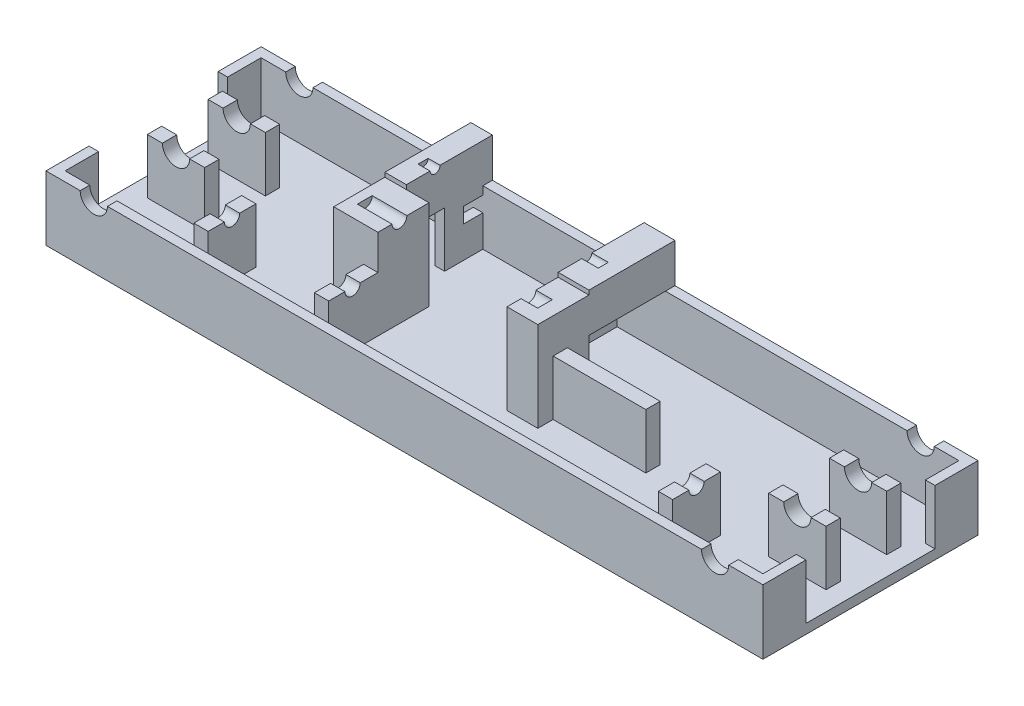
SolidWorks part; units mm, degrees
ref_plane "前视基准面" through (0, 0, 0) normal (0, 0, 1) x (1, 0, 0)
ref_plane "上视基准面" through (0, 0, 0) normal (0, 1, 0) x (1, 0, 0)
ref_plane "右视基准面" through (0, 0, 0) normal (1, 0, 0) x (0, 0, -1)
other "Configuration Table"
sketch "草图1" plane through (0, 0, 0) normal (0, 1, 0) x (1, 0, 0)
  line L1 (-75, -22.5) -> (75, -22.5)
  line L2 (-75, -22.5) -> (-75, 22.5)
  line L3 (-75, 22.5) -> (75, 22.5)
  line L4 (75, -22.5) -> (75, 22.5)
  line L5 (-75, -22.5) -> (75, 22.5) construction
  line L6 (-75, 22.5) -> (75, -22.5) construction
  point P0 (0, 0)
  dimension "D1" = 150
  dimension "D2" = 45
extrude "凸台-拉伸1" add sketch "草图1" along normal blind 2
sketch "草图2" plane through (0, 2, 0) normal (0, 1, 0) x (1, 0, 0)
  line L0 (-75, 22.5) -> (75, 22.5)
  line L1 (75, 22.5) -> (75, 13.5)
  line L2 (75, -22.5) -> (75, 22.5) construction
  line L3 (75, -22.5) -> (-75, -22.5)
  line L4 (-75, -22.5) -> (-75, -13.5)
  line L5 (-73, 20.5) -> (-28.6, 20.5)
  line L6 (73, 20.5) -> (73, 13.5)
  line L7 (73, -20.5) -> (-73, -20.5)
  line L8 (-73, -20.5) -> (-73, -13.5)
  line L9 (1.5, 20.5) -> (73, 20.5)
  line L23 (-1, 20.5) -> (-1, 12.5)
  line L24 (-73, 13.5) -> (-75, 13.5)
  line L25 (-75, -13.5) -> (-73, -13.5)
  line L26 (75, 13.5) -> (73, 13.5)
  line L27 (75, -13.5) -> (73, -13.5)
  line L28 (-75, 13.5) -> (-75, 22.5)
  line L29 (-73, 13.5) -> (-73, 20.5)
  line L30 (73, -13.5) -> (73, -20.5)
  line L31 (75, -13.5) -> (75, -22.5)
  line L32 (-1, 12.5) -> (1.5, 12.5)
  line L33 (-71, -2.3) -> (-59, -2.3)
  line L34 (-71, -2.3) -> (-71, -5.3)
  line L35 (-71, -5.3) -> (-59, -5.3)
  line L36 (-59, -2.3) -> (-59, -5.3)
  line L37 (-75, 22.5) -> (-75, -22.5) construction
  line L38 (59, -2.3) -> (71, -2.3)
  line L39 (59, -2.3) -> (59, -5.3)
  line L40 (59, -5.3) -> (71, -5.3)
  line L41 (71, -2.3) -> (71, -5.3)
  line L42 (75, -22.5) -> (75, 22.5) construction
  line L43 (-55, -5.4) -> (-75, -5.4) construction
  line L44 (75, -5.4) -> (55, -5.4) construction
  line L45 (66.4142, 10.5) -> (67.4958, 10.5) construction
  line L46 (-71, 10.4) -> (-59, 10.4)
  line L47 (-71, 10.4) -> (-71, 7.4)
  line L48 (-71, 7.4) -> (-59, 7.4)
  line L49 (-59, 10.4) -> (-59, 7.4)
  line L50 (59, 10.4) -> (71, 10.4)
  line L51 (59, 10.4) -> (59, 7.4)
  line L52 (59, 7.4) -> (71, 7.4)
  line L53 (71, 10.4) -> (71, 7.4)
  line L54 (-63.5858, 10.5) -> (-62.5042, 10.5) construction
  line L55 (1.5, 20.5) -> (1.5, 12.5)
  line L57 (-28.6, 20.5) -> (-28.6, 12.5)
  line L58 (-28.6, 12.5) -> (-26.6, 12.5)
  line L59 (-26.6, 20.5) -> (-26.6, 12.5)
  line L60 (-26.6, 20.5) -> (-1, 20.5)
  point P57 (-26.6, 16.5)
  dimension "D1" = 2
  dimension "D2" = 2
  dimension "D3" = 2
  dimension "D4" = 2
  dimension "D5" = 9
  dimension "D6" = 3
  dimension "D7" = 3
  dimension "D8" = 12
  dimension "D9" = 12
  dimension "D10" = 4
  dimension "D11" = 4
  dimension "D12" = 0.1
  dimension "D13" = 0.1
  dimension "D14" = 0.1
  dimension "D15" = 0.1
  dimension "D16" = 3
  dimension "D17" = 2.5
  dimension "D18" = 2
  dimension "D19" = 71.5
  dimension "D20" = 8
  dimension "D21" = 48.4
extrude "凸台-拉伸2" add sketch "草图2" along normal up to surface (11.5 mm away)
sketch "草图4" plane through (0, 2, 0) normal (0, 1, 0) x (1, 0, 0)
  line L1 (-50.0747, -6.5) -> (-47.0747, -6.5)
  line L2 (-50.0747, -6.5) -> (-50.0747, -16.5)
  line L3 (-50.0747, -16.5) -> (-47.0747, -16.5)
  line L4 (-47.0747, -6.5) -> (-47.0747, -16.5)
  line L5 (-31.1, 4.5) -> (-21.85, 4.5)
  line L6 (-31.1, 4.5) -> (-31.1, -6.2)
  line L7 (-24.85, -16.5) -> (-21.85, -16.5)
  line L8 (-21.85, 4.5) -> (-21.85, -16.5)
  line L9 (47.1147, -6.5) -> (50.1147, -6.5)
  line L10 (47.1147, -6.5) -> (47.1147, -16.5)
  line L11 (47.1147, -16.5) -> (50.1147, -16.5)
  line L12 (50.1147, -6.5) -> (50.1147, -16.5)
  line L13 (5.15, 4.5) -> (11.6, 4.5)
  line L14 (5.15, 4.5) -> (5.15, -6.2)
  line L15 (5.15, -6.2) -> (11.6, -6.2)
  line L16 (11.6, 4.5) -> (11.6, 0)
  line L26 (31, 0) -> (11.6, 0)
  line L28 (11.6, -3) -> (31, -3)
  line L31 (-50.2747, -15.25) -> (-50.2747, -7.75) construction
  line L32 (50.3147, -7.75) -> (50.3147, -15.25) construction
  line L33 (-29.7348, -10) -> (-29.7348, -13) construction
  line L34 (56.24, -10) -> (-56.2, -10) construction
  line L35 (-56.2, -13) -> (56.24, -13) construction
  line L36 (-29.7348, -11.5) -> (-37.5732, -11.5) construction
  line L37 (-21.55, -10.8234) -> (-21.55, -11.245) construction
  line L38 (31, 0) -> (31, -3)
  line L40 (11.6, -3) -> (11.6, -6.2)
  line L41 (75, -13.5) -> (75, 13.5) construction
  line L42 (-26.35, -3.2) -> (7.05, -3.2) construction
  line L43 (-31.1, -6.2) -> (-24.85, -6.2)
  line L44 (-24.85, -6.2) -> (-24.85, -16.5)
  line L45 (11.7, 3.8856) -> (11.7, 17.1144) construction
  line L46 (5.05, 2.196) -> (5.05, 3.4405) construction
  line L47 (-75, 13.5) -> (-75, -13.5) construction
  line L48 (-73, 20.5) -> (-28.6, 20.5) construction
  dimension "D1" = 3
  dimension "D2" = 43.9
  dimension "D3" = 3
  dimension "D4" = 10
  dimension "D5" = 0.2
  dimension "D6" = 0.2
  dimension "D7" = 0.3
  dimension "D8" = 16
  dimension "D9" = 44
  dimension "D10" = 3
  dimension "D11" = 3
  dimension "D12" = 0.1
  dimension "D13" = 3
  dimension "D14" = 0.1
extrude "凸台-拉伸3" add sketch "草图4" along normal up to surface (11.5 mm away) up to face at (-6.8375, 13.5, -17)
sketch "草图5" plane through (0, 0, 22.5) normal (0, 0, 1) x (1, 0, 0)
  circle A0 centre (-65, 13.5) radius 2.85
  arc A1 (-63.05, 11.5609) -> (-63.05, 15.4391) centre (-65, 13.5) ccw construction
  circle A2 centre (65, 13.5) radius 2.85
  arc A3 (66.95, 11.5609) -> (66.95, 15.4391) centre (65, 13.5) ccw construction
  dimension "D1" = 0.1
  dimension "D2" = 0.1
extrude "切除-拉伸1" cut sketch "草图5" against normal up to surface (45 mm away) up to face at (0, 6.75, -22.5)
sketch "草图6" plane through (50.1147, 0, 0) normal (1, 0, 0) x (0, 0, -1)
  line L0 (-16.5, 13.5) -> (-6.5, 13.5) construction
  circle A0 centre (-11.5, 13.5) radius 1.6
  circle A1 centre (-11.5, 13.5) radius 1.5 construction
  dimension "D1" = 0.1
extrude "切除-拉伸2" cut sketch "草图6" against normal up to surface (125.1147 mm away) up to face at (-75, 7.25, 0)
sketch "草图7" plane through (0, 13.5, 0) normal (0, 1, 0) x (1, 0, 0)
  line L0 (5.15, 22.5) -> (5.15, -6.2)
  line L3 (5.15, 22.5) -> (11.6, 22.5)
  line L4 (11.6, -6.2) -> (11.6, 22.5)
  line L5 (-26.6, 22.5) -> (-26.6, 4.5)
  line L6 (-26.6, 4.5) -> (-21.85, 4.5)
  line L7 (-21.85, 4.5) -> (-21.85, -6.2)
  line L8 (-21.85, -9.9) -> (-21.85, 4.5) construction
  line L9 (-21.85, -6.2) -> (-31.1, -6.2)
  line L10 (-31.1, -6.2) -> (-31.1, 22.5)
  line L11 (-31.1, 22.5) -> (-26.6, 22.5)
  line L12 (-21.85, 4.5) -> (-31.1, 4.5) construction
  line L13 (62.15, 22.5) -> (-62.15, 22.5) construction
  line L14 (5.15, -6.2) -> (11.6, -6.2)
  line L15 (-75, 22.5) -> (-75, 13.5) construction
  line L17 (11.6, -6.2) -> (11.6, -3) construction
  dimension "D2" = 48.4
  dimension "D3" = 4.5
extrude "凸台-拉伸6" add sketch "草图7" along normal up to surface (7.3 mm away)
sketch "草图8" plane through (0, 20.8, 0) normal (0, 1, 0) x (1, 0, 0)
  line L1 (-31.1, 22.5) -> (-26.6, 22.5)
  line L2 (-31.1, 22.5) -> (-31.1, 4.5)
  line L3 (-31.1, 4.5) -> (-26.6, 4.5)
  line L4 (-26.6, 22.5) -> (-26.6, 4.5)
  line L5 (5.15, 22.5) -> (11.6, 22.5)
  line L6 (5.15, 22.5) -> (5.15, 4.5)
  line L7 (5.15, 4.5) -> (11.6, 4.5)
  line L8 (11.6, 22.5) -> (11.6, 4.5)
extrude "凸台-拉伸7" add sketch "草图8" along normal up to surface (0.9 mm away)
sketch "草图9" plane through (11.6, 0, 0) normal (1, 0, 0) x (0, 0, -1)
  circle A0 centre (10.5, 21.7) radius 1.05
  circle A1 centre (-1.7, 20.8) radius 1.55
  circle A2 centre (10.5, 21.7) radius 1 construction
  circle A3 centre (-1.7, 20.8) radius 1.5 construction
  dimension "D1" = 0.05
  dimension "D2" = 0.05
extrude "切除-拉伸3" cut sketch "草图9" against normal offset from surface (37.7 mm away) 2 from offset 3 up to face at (-31.1, 14.3889, -7.9) offset against normal yes
sketch "草图10" plane through (1.5, 0, 0) normal (1, 0, 0) x (0, 0, -1)
  line L0 (20.5, 13.5) -> (20.5, 2) construction
  line L1 (16.5, 11.8) -> (20.5, 11.8)
  line L2 (16.5, 11.8) -> (16.5, 8.6)
  line L3 (16.5, 8.6) -> (20.5, 8.6)
  line L4 (20.5, 11.8) -> (20.5, 8.6)
  line L5 (16.6, 8.7) -> (20.4, 8.7) construction
  line L9 (16.6, 11.7) -> (20.4, 11.7) construction
  line L10 (16.6, 11.7) -> (16.6, 8.7) construction
  dimension "D1" = 0.1
  dimension "D2" = 0.1
  dimension "D3" = 0.1
extrude "切除-拉伸4" cut sketch "草图10" against normal up to surface (30.1 mm away) up to face at (-28.6, 7.75, -16.5)
